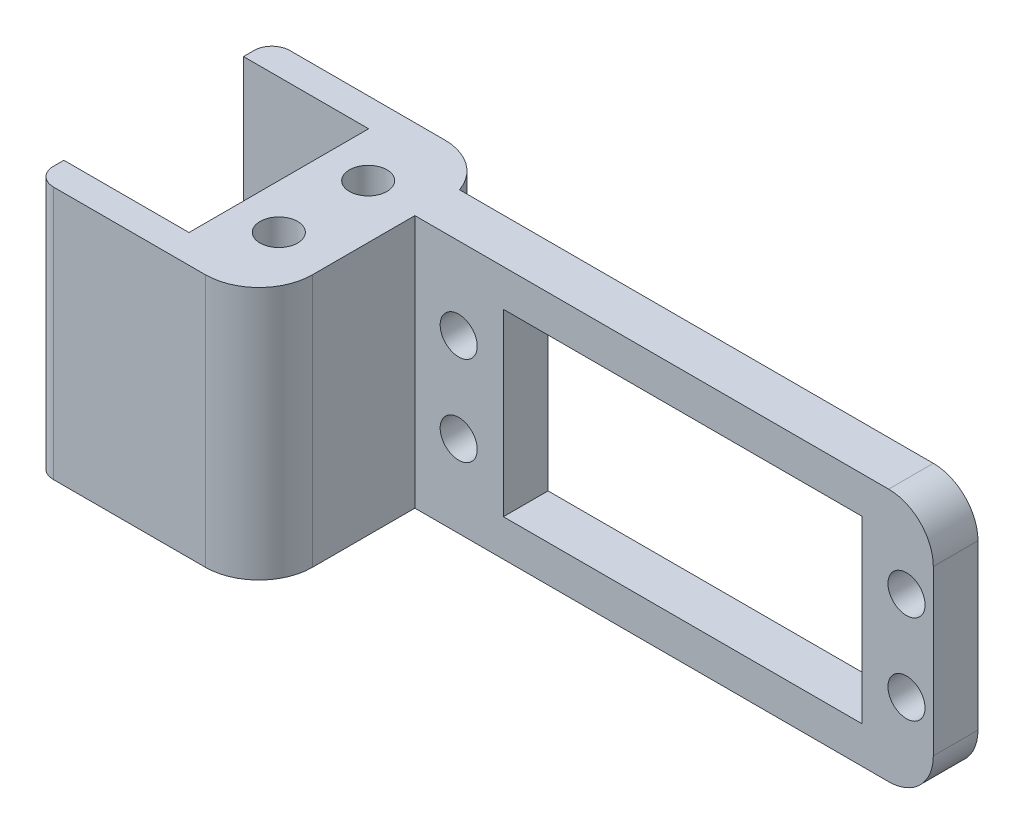
SolidWorks part; units mm, degrees
ref_plane "Front Plane" through (0, 0, 0) normal (0, 0, 1) x (1, 0, 0)
ref_plane "Top Plane" through (0, 0, 0) normal (0, 1, 0) x (1, 0, 0)
ref_plane "Right Plane" through (0, 0, 0) normal (1, 0, 0) x (0, 0, -1)
sketch "Sketch1" plane through (0, 0, 0) normal (0, 1, 0) x (1, 0, 0)
  line L0 (0, 0) -> (14, 0)
  line L1 (14, 0) -> (14, -20.1)
  line L2 (14, -20.1) -> (0, -20.1)
  line L3 (0, -20.1) -> (0, -23.275)
  line L4 (0, -23.275) -> (25, -23.275)
  line L5 (25, -23.275) -> (25, 3.175)
  line L6 (25, 3.175) -> (0, 3.175)
  line L7 (0, 3.175) -> (0, 0)
  line L8 (19, -5.05) -> (19, -15.05) construction
  circle A0 centre (19, -5.05) radius 2.1
  circle A1 centre (19, -15.05) radius 2.1
  point P13 (19, -10.05)
  point P14 (14, -10.05)
  dimension "D1" = 4.2
  dimension "D2" = 10
  dimension "D3" = 3.175
  dimension "D4" = 14
  dimension "D5" = 5
  dimension "D6" = 20.1
  dimension "D7" = 25
extrude "Boss-Extrude1" add sketch "Sketch1" along normal blind 28.35
sketch "Sketch2" plane through (25, 0, 0) normal (1, 0, 0) x (0, 0, -1)
  line L0 (3.175, 28.35) -> (3.175, 0) construction
  line L1 (-0.825, 28.35) -> (-5.825, 28.35)
  line L2 (-0.825, 28.35) -> (-0.825, 0)
  line L3 (-0.825, 0) -> (-5.825, 0)
  line L4 (-5.825, 28.35) -> (-5.825, 0)
  line L5 (-0.825, 28.35) -> (-5.825, 0) construction
  line L6 (-0.825, 0) -> (-5.825, 28.35) construction
  line L7 (-23.275, 28.35) -> (3.175, 28.35) construction
  point P0 (-3.325, 14.175)
  point P5 (3.175, 14.175)
  dimension "D1" = 4
  dimension "D2" = 5
extrude "Boss-Extrude2" add sketch "Sketch2" along normal blind 58
sketch "Sketch3" plane through (0, 0, 0.825) normal (0, 0, -1) x (-1, 0, 0)
  line L0 (-83, 0) -> (-83, 28.35) construction
  line L1 (-34.9, 4.125) -> (-75, 4.125)
  line L2 (-34.9, 4.125) -> (-34.9, 24.225)
  line L3 (-34.9, 24.225) -> (-75, 24.225)
  line L4 (-75, 4.125) -> (-75, 24.225)
  line L5 (-34.9, 4.125) -> (-75, 24.225) construction
  line L6 (-34.9, 24.225) -> (-75, 4.125) construction
  line L7 (-83, 0) -> (-83, 28.35) construction
  point P0 (-54.95, 14.175)
  point P5 (-83, 14.175)
  dimension "D1" = 20.1
  dimension "D2" = 40.1
  dimension "D3" = 8
extrude "Cut-Extrude1" cut sketch "Sketch3" against normal through all both and the other way through all
sketch "Sketch4" plane through (0, 0, 0.825) normal (0, 0, -1) x (-1, 0, 0)
  arc A0 (-81.8181, 18.175) -> (-81.8181, 20.175) centre (-80, 19.175) ccw construction
  arc A1 (-81.8181, 8.175) -> (-81.8181, 10.175) centre (-80, 9.175) ccw construction
  arc A2 (-28.0819, 20.175) -> (-28.0819, 18.175) centre (-29.9, 19.175) ccw construction
  arc A3 (-28.0819, 10.175) -> (-28.0819, 8.175) centre (-29.9, 9.175) ccw construction
  arc A4 (-81.8181, 18.175) -> (-81.8181, 20.175) centre (-80, 19.175) ccw construction
  arc A5 (-81.8181, 8.175) -> (-81.8181, 10.175) centre (-80, 9.175) ccw construction
  arc A6 (-28.0819, 20.175) -> (-28.0819, 18.175) centre (-29.9, 19.175) ccw construction
  arc A7 (-28.0819, 10.175) -> (-28.0819, 8.175) centre (-29.9, 9.175) ccw construction
  circle A8 centre (-29.9, 19.175) radius 2.075
  circle A9 centre (-29.9, 9.175) radius 2.075
  circle A10 centre (-80, 19.175) radius 2.075
  circle A11 centre (-80, 9.175) radius 2.075
extrude "Cut-Extrude2" cut sketch "Sketch4" against normal through all both and the other way through all
fillet "Fillet1" radius 6 2 edges at (25, 14.175, 23.275) (25, 14.175, -3.175)
fillet "Fillet2" radius 5 2 edges at (83, 0, 3.325) (83, 28.35, 3.325)
fillet "Fillet3" radius 2 2 edges at (0, 14.175, 23.275) (0, 14.175, -3.175)
